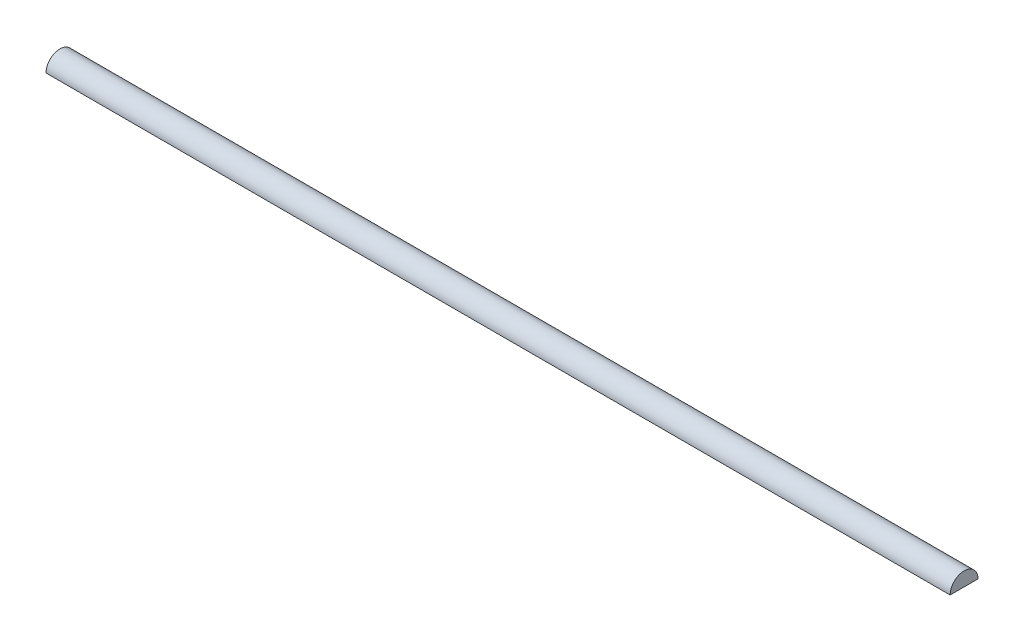
SolidWorks part; units mm, degrees
ref_plane "Front Plane" through (0, 0, 0) normal (0, 0, 1) x (1, 0, 0)
ref_plane "Top Plane" through (0, 0, 0) normal (0, 1, 0) x (1, 0, 0)
ref_plane "Right Plane" through (0, 0, 0) normal (1, 0, 0) x (0, 0, -1)
sketch "Sketch1" plane through (0, 0, 0) normal (0, 1, 0) x (-1, 0, 0)
  line L0 (2034.2432, 337.92) -> (227.583, 983.35)
  line L1 (2034.2432, 337.92) -> (3247.5197, 368.69)
  line L2 (3247.5197, 368.69) -> (3247.5197, 0)
  line L3 (3247.5197, 0) -> (8763.0034, 0)
  line L4 (8763.0034, 0) -> (8763.0034, 1070)
  line L5 (9493.3879, 1120) -> (10227.583, 1070)
  line L6 (10227.583, 1070) -> (8763.0034, 1070)
  line L7 (9493.3879, 1120) -> (5509.8238, 1120)
  line L8 (227.583, 983.35) -> (5509.8238, 1120)
  dimension "D1" = 368.69
  dimension "D2" = 1070
  dimension "D3" = 10000
  dimension "D4" = 50
  dimension "D5" = 337.92
  dimension "D6" = 983.35
revolve "Revolve1" add sketch "Sketch1" angle 360 about L3
sketch "Sketch2" plane through (0, 0, 0) normal (1, 0, 0) x (0, 0, -1)
  circle A0 centre (0, 0) radius 1232.8576
extrude "Boss-Extrude1" add sketch "Sketch2" along normal blind 40000 and the other way blind 40000 separate body
combine bodies "Combine1" operation type subtract main body 102 bodies to subtract 101
sketch "Sketch3" plane through (0, 0, 0) normal (0, 1, 0) x (-1, 0, 0)
  line L0 (40000, -1232.8576) -> (40000, 1232.8576) construction
  line L1 (-40000, 2080.3524) -> (40000, 2080.3524)
  line L2 (-40000, 2080.3524) -> (-40000, -1559.5909)
  line L3 (-40000, -1559.5909) -> (40000, -1559.5909)
  line L4 (40000, 2080.3524) -> (40000, -1559.5909)
  line L5 (-40000, 1232.8576) -> (-40000, -1232.8576) construction
extrude "Cut-Extrude1" cut sketch "Sketch3" against normal through all
